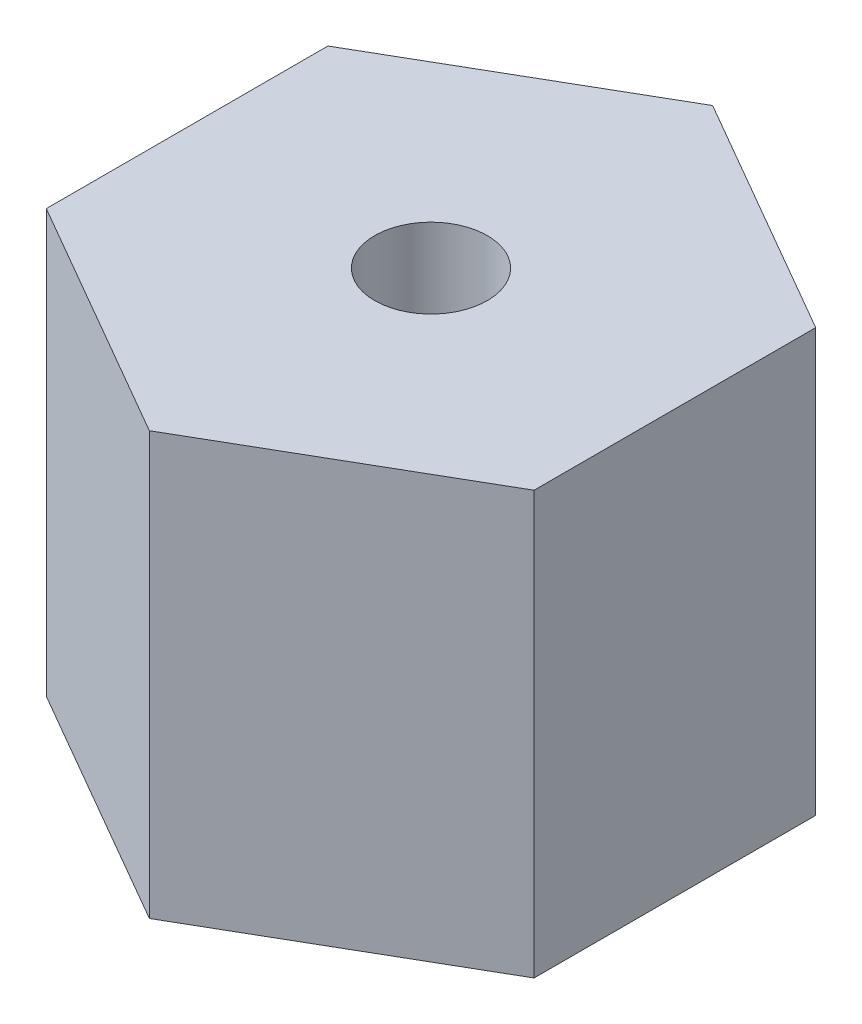
SolidWorks part; units mm, degrees
ref_plane "Front Plane" through (0, 0, 0) normal (0, 0, 1) x (1, 0, 0)
ref_plane "Top Plane" through (0, 0, 0) normal (0, 1, 0) x (1, 0, 0)
ref_plane "Right Plane" through (0, 0, 0) normal (1, 0, 0) x (0, 0, -1)
sketch "Sketch2" plane through (0, 0, 0) normal (0, 1, 0) x (1, 0, 0)
  line L1 (0, 10) -> (-8.6603, 5)
  line L2 (-8.6603, 5) -> (-8.6603, -5)
  line L3 (-8.6603, -5) -> (0, -10)
  line L4 (0, -10) -> (8.6603, -5)
  line L5 (8.6603, -5) -> (8.6603, 5)
  line L6 (8.6603, 5) -> (0, 10)
  circle A0 centre (0, 0) radius 3
  circle A1 centre (0, 0) radius 10 construction
  circle A2 centre (0, 0) radius 2
  dimension "D1" = 6
  dimension "D2" = 20
  dimension "D3" = 4
extrude "Boss-Extrude1" add sketch "Sketch2" along normal blind 15 contours A0 | L5 L6 L1 L2 L3 L4 A0 region at (4.1978, 0, -7.2709) region at (-2.9151, 0, 0)
extrude "Cut-Extrude1" cut sketch "Sketch2<4>" along normal blind 9 contours A0 region at (-2.9151, 0, 0)
sketch "Sketch2<4>" plane through (0, 0, 0) normal (0, 1, 0) x (1, 0, 0) same geometry as "Sketch2"
chamfer "Chamfer1" [suppressed] distance 3 angle 45
